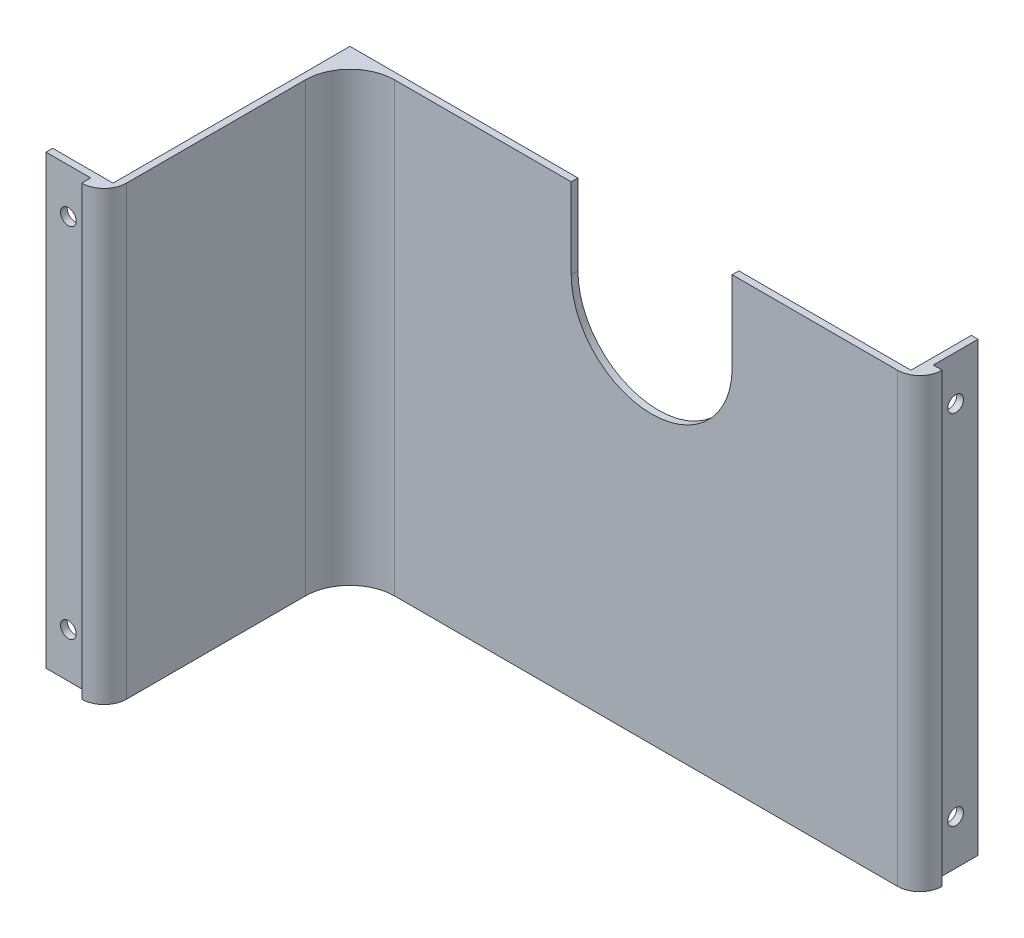
SolidWorks part; units mm, degrees
material "ABS"
ref_plane "Спереди" through (0, 0, 0) normal (0, 0, 1) x (1, 0, 0)
ref_plane "Сверху" through (0, 0, 0) normal (0, 1, 0) x (1, 0, 0)
ref_plane "Справа" through (0, 0, 0) normal (1, 0, 0) x (0, 0, -1)
sketch "Эскиз1" plane through (0, 0, 0) normal (0, 1, 0) x (1, 0, 0)
  line L0 (0, 0) -> (-112.5, 0)
  line L1 (-122.5, -10) -> (-122.5, -50)
  line L2 (-127.5, -55) -> (-127.5, -53)
  line L3 (-127.5, -53) -> (-137.5, -53)
  line L4 (5, 5) -> (3, 5)
  line L5 (3, 5) -> (3, 15)
  line L6 (3, 15) -> (1.5, 15)
  line L7 (0, 0) -> (0, 1.5) construction
  line L8 (1.5, 15) -> (1.5, 1.5)
  line L9 (-122.5, -50) -> (-124, -50) construction
  line L10 (-137.5, -53) -> (-137.5, -51.5)
  line L11 (-137.5, -51.5) -> (-124, -51.5)
  line L12 (-124, -51.5) -> (-124, 1.5)
  line L13 (-124, 1.5) -> (1.5, 1.5)
  arc A0 (-112.5, 0) -> (-122.5, -10) centre (-112.5, -10) ccw
  arc A1 (-122.5, -50) -> (-127.5, -55) centre (-127.5, -50) cw
  arc A2 (0, 0) -> (5, 5) centre (0, 5) ccw
  dimension "D1" = 112.5
  dimension "D2" = 5
  dimension "D6" = 10
  dimension "D9" = 5
  dimension "D3" = 2
  dimension "D4" = 1.5
  dimension "D5" = 1.5
  dimension "D7" = 1.5
  dimension "D8" = 40
  dimension "D10" = 2
  dimension "D11" = 1.5
  dimension "D12" = 10
  dimension "D13" = 10
extrude "Бобышка-Вытянуть1" add sketch "Эскиз1" along normal blind 100
sketch "Эскиз2" plane through (0, 0, 0) normal (0, 0, 1) x (1, 0, 0)
  line L8 (-73, 100) -> (-37, 100)
  line L9 (-73, 82) -> (-73, 100)
  line L10 (-37, 100) -> (-37, 82)
  line L11 (5, 100) -> (-37, 100) construction
  arc A1 (-73, 82) -> (-37, 82) centre (-55, 82) ccw
  point P0 (0, 0)
  dimension "D4" = 18
  dimension "D1" = 42
  dimension "D2" = 36
  dimension "D3" = 18
extrude "Вырез-Вытянуть1" cut sketch "Эскиз2" against normal blind 10
sketch "Эскиз3" plane through (3, 0, 0) normal (1, 0, 0) x (0, 0, -1)
  line L0 (10, 100) -> (10, 0) construction
  line L1 (5, 100) -> (15, 100) construction
  line L2 (5, 0) -> (15, 0) construction
  line L3 (15, 50) -> (5, 50) construction
  line L4 (15, 100) -> (15, 0) construction
  line L5 (5, 100) -> (5, 0) construction
  circle A0 centre (10, 90) radius 1.75
  circle A1 centre (10, 10) radius 1.75
  dimension "D1" = 3.5
  dimension "D2" = 10
extrude "Вырез-Вытянуть2" cut sketch "Эскиз3" against normal blind 10
sketch "Эскиз4" plane through (0, 0, 53) normal (0, 0, 1) x (1, 0, 0)
  line L0 (-132.5, 100) -> (-132.5, 0) construction
  line L1 (-137.5, 100) -> (-127.5, 100) construction
  line L2 (-137.5, 0) -> (-127.5, 0) construction
  line L3 (-137.5, 50) -> (-127.5, 50) construction
  line L4 (-137.5, 100) -> (-137.5, 0) construction
  line L5 (-127.5, 100) -> (-127.5, 0) construction
  circle A0 centre (-132.5, 90) radius 1.75
  circle A1 centre (-132.5, 10) radius 1.75
  dimension "D1" = 3.5
  dimension "D2" = 10
extrude "Вырез-Вытянуть3" cut sketch "Эскиз4" against normal blind 10
